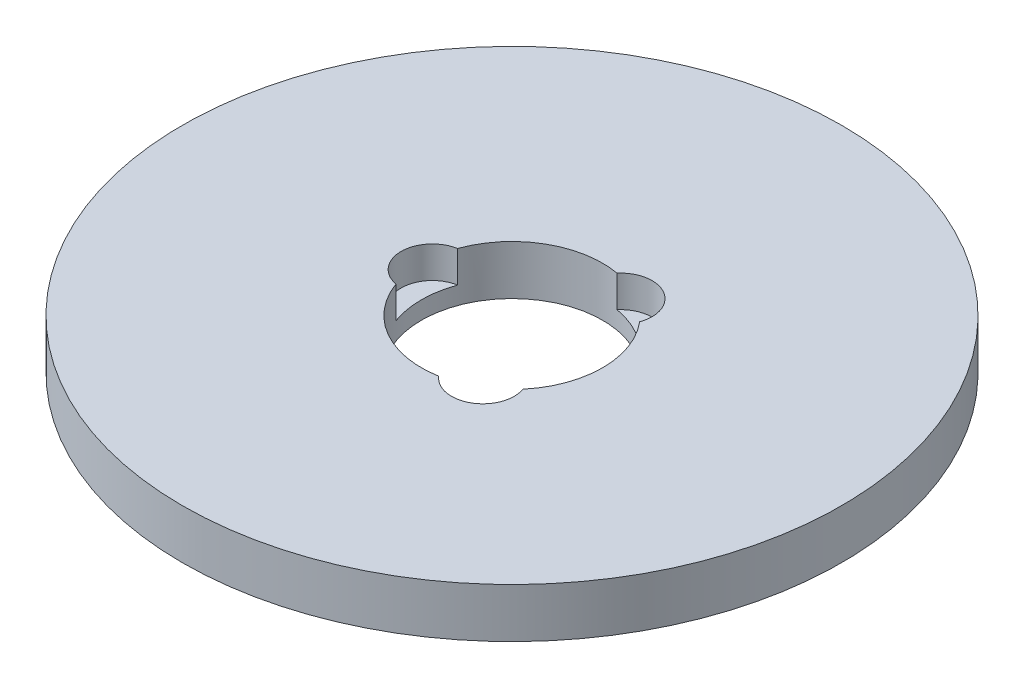
SolidWorks part; units mm, degrees
ref_plane "Front Plane" through (0, 0, 0) normal (0, 0, 1) x (1, 0, 0)
ref_plane "Top Plane" through (0, 0, 0) normal (0, 1, 0) x (1, 0, 0)
ref_plane "Right Plane" through (0, 0, 0) normal (1, 0, 0) x (0, 0, -1)
sketch "Sketch1" plane through (0, 0, 0) normal (0, 1, 0) x (1, 0, 0)
  circle A0 centre (0, 0) radius 100
  dimension "FLANGE_OD" = 200
extrude "Boss-Extrude1" add sketch "Sketch1" along normal blind 15
sketch "Sketch2" plane through (0, 0, 0) normal (0, 1, 0) x (1, 0, 0)
  circle A0 centre (0, 0) radius 27.5
  dimension "BORE_D" = 55
extrude "Cut-Extrude1" cut sketch "Sketch2" along normal through all
sketch "Sketch3" plane through (0, 15, 0) normal (0, 1, 0) x (1, 0, 0)
  circle A0 centre (0, 0) radius 24.1527 construction
  circle A1 centre (-24.1527, 0) radius 9.5091
  dimension "BOLT_D" = 19.0183
  dimension "BOLT_PCD" = 48.3053
extrude "Cut-Extrude2" cut sketch "Sketch3" against normal blind 9.6193
pattern_circular "CirPattern1" count 3 over 360 about axis through (0, 0, 0) along (0, 1, 0) of "Cut-Extrude2"
